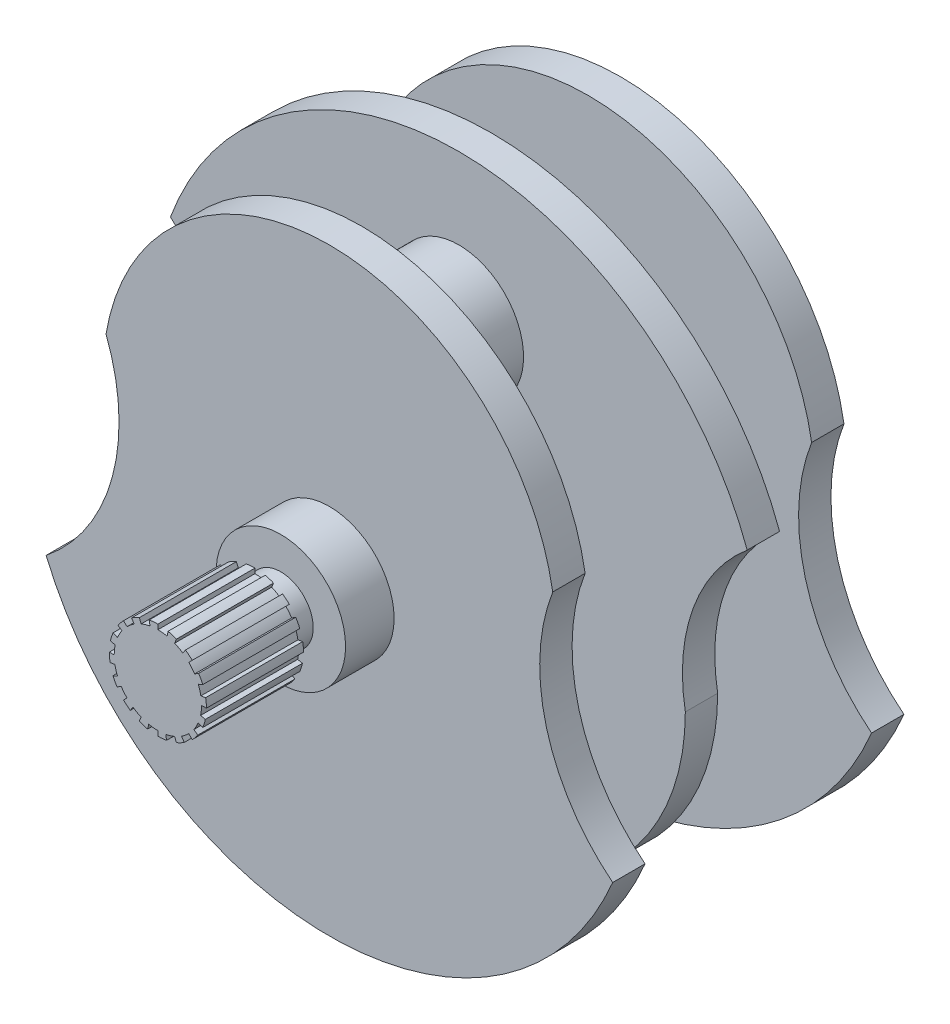
SolidWorks part; units mm, degrees
ref_plane "Front Plane" through (0, 0, 0) normal (0, 0, 1) x (1, 0, 0)
ref_plane "Top Plane" through (0, 0, 0) normal (0, 1, 0) x (1, 0, 0)
ref_plane "Right Plane" through (0, 0, 0) normal (1, 0, 0) x (0, 0, -1)
sketch "Sketch1" plane through (0, 0, 0) normal (0, 0, 1) x (1, 0, 0)
  circle A0 centre (0, 0) radius 20
  dimension "D1" = 20
extrude "Boss-Extrude1" add sketch "Sketch1" along normal blind 15
sketch "Sketch2" plane through (0, 0, 15) normal (0, 0, 1) x (1, 0, 0)
  circle A0 centre (0, 0) radius 10
  dimension "D1" = 10
extrude "Boss-Extrude2" add sketch "Sketch2" along normal blind 8
sketch "Sketch3" plane through (0, 0, 23) normal (0, 0, 1) x (1, 0, 0)
  circle A0 centre (0, 0) radius 15
  dimension "D1" = 15
extrude "Boss-Extrude3" add sketch "Sketch3" along normal blind 30
sketch "Sketch5" plane through (0, 0, 53) normal (0, 0, 1) x (1, 0, 0)
  line L0 (0, 15) -> (0, 13.5)
  line L1 (2.8421, 13.1974) -> (3.1579, 14.6638)
  circle A0 centre (0, 0) radius 15 construction
  arc A1 (0, 13.5) -> (2.8421, 13.1974) centre (0, 0) cw
  arc A2 (3.1579, 14.6638) -> (0, 15) centre (0, 0) ccw
  circle A3 centre (0, 0) radius 15
  point P8 (0, 14.25)
  point P9 (0, 0)
  circle M6 centre (0, 0) radius 15
  dimension "D1" = 13.5
  dimension "D2" = 3
extrude "Cut-Extrude1" cut sketch "Sketch5" against normal up to next contours L0 A1 L1 M6 region at (1.507, 14.1564, 53)
pattern_circular "CirPattern1" count 16 over 360 about axis through (0, 0, 53) along (0, 0, 1) of "Cut-Extrude1"
sketch "Sketch8" plane through (0, 0, 0) normal (0, 0, -1) x (-1, 0, 0)
  arc A0 (69.0293, 31.6168) -> (-69.0293, 31.6168) centre (0, 20) ccw
  arc A5 (-87.5502, -36.8776) -> (87.5502, -36.8776) centre (0, 0) ccw
  arc A6 (-69.0293, 31.6168) -> (-87.5502, -36.8776) centre (-125, 10) cw
  arc A7 (69.0293, 31.6168) -> (87.5502, -36.8776) centre (125, 10) ccw
  point P9 (0, 0)
  point P10 (0, 0)
  point P11 (0, 32.6586)
  point P12 (-88.5936, -32.8967)
  point P13 (0, 0)
  point P14 (0, -16.2678)
  point P15 (0, 0)
  point P16 (-125.2365, 10)
  dimension "D1" = 70
  dimension "D2" = 95
  dimension "D4" = 60
  dimension "D3" = 20
  dimension "D5" = 10
  dimension "D6" = 125
extrude "Boss-Extrude5" add sketch "Sketch8" along normal blind 10
sketch "Sketch9" plane through (0, 0, -10) normal (0, 0, -1) x (-1, 0, 0)
  circle A0 centre (0, 50) radius 20
  point P2 (0, 0)
  dimension "D2" = 20
  dimension "D1" = 50
extrude "Boss-Extrude6" add sketch "Sketch9" along normal blind 30
sketch "Sketch10" plane through (0, 0, -40) normal (0, 0, -1) x (-1, 0, 0)
  arc A0 (-70, -20) -> (70, -20) centre (0, -20) ccw
  arc A1 (-70, -20) -> (-89.1301, 32.876) centre (-125, -10) ccw
  arc A2 (70, -20) -> (89.1301, 32.876) centre (125, -10) cw
  arc A3 (-89.1301, 32.876) -> (89.1301, 32.876) centre (0, 0) cw
  point P1 (0, 0)
  dimension "D1" = 70
  dimension "D3" = 95
  dimension "D2" = 20
  dimension "D4" = 125
  dimension "D5" = 10
extrude "Boss-Extrude7" add sketch "Sketch10" along normal blind 10
ref_plane "Plane3" through (0, 0, -80) normal (0, 0, -1) x (-1, 0, 0)
sketch "Sketch12" plane through (0, 0, -80) normal (0, 0, -1) x (-1, 0, 0)
  arc A4 (69.0293, 31.6168) -> (-69.0293, 31.6168) centre (0, 20) ccw
  arc A5 (-87.5502, -36.8776) -> (-69.0293, 31.6168) centre (-125, 10) ccw
  arc A6 (-87.5502, -36.8776) -> (87.5502, -36.8776) centre (0, 0) ccw
  arc A7 (69.0293, 31.6168) -> (87.5502, -36.8776) centre (125, 10) ccw
  arc A8 (69.0293, 31.6168) -> (-69.0293, 31.6168) centre (0, 20) ccw
  arc A9 (-87.5502, -36.8776) -> (-69.0293, 31.6168) centre (-125, 10) ccw
  arc A10 (-87.5502, -36.8776) -> (87.5502, -36.8776) centre (0, 0) ccw
  arc A11 (69.0293, 31.6168) -> (87.5502, -36.8776) centre (125, 10) ccw
  dimension "D1" = 0
extrude "Boss-Extrude8" add sketch "Sketch12" along normal blind 10 separate body
sketch "Sketch14" plane through (0, 0, -50) normal (0, 0, -1) x (-1, 0, 0)
  circle A0 centre (0, -50) radius 20
  point P2 (0, 0)
  dimension "D2" = 20
  dimension "D1" = 50
extrude "Boss-Extrude9" add sketch "Sketch14" along normal up to next
sketch "Sketch15" plane through (0, 0, -90) normal (0, 0, -1) x (-1, 0, 0)
  circle A1 centre (0, 0) radius 20
  circle A2 centre (0, 0) radius 20
  dimension "D1" = 0
extrude "Boss-Extrude10" add sketch "Sketch15" along normal blind 15
sketch "Sketch16" plane through (0, 0, -105) normal (0, 0, -1) x (-1, 0, 0)
  circle A1 centre (0, 0) radius 10
  circle A2 centre (0, 0) radius 10
  dimension "D1" = 0
extrude "Boss-Extrude11" add sketch "Sketch16" along normal blind 8
